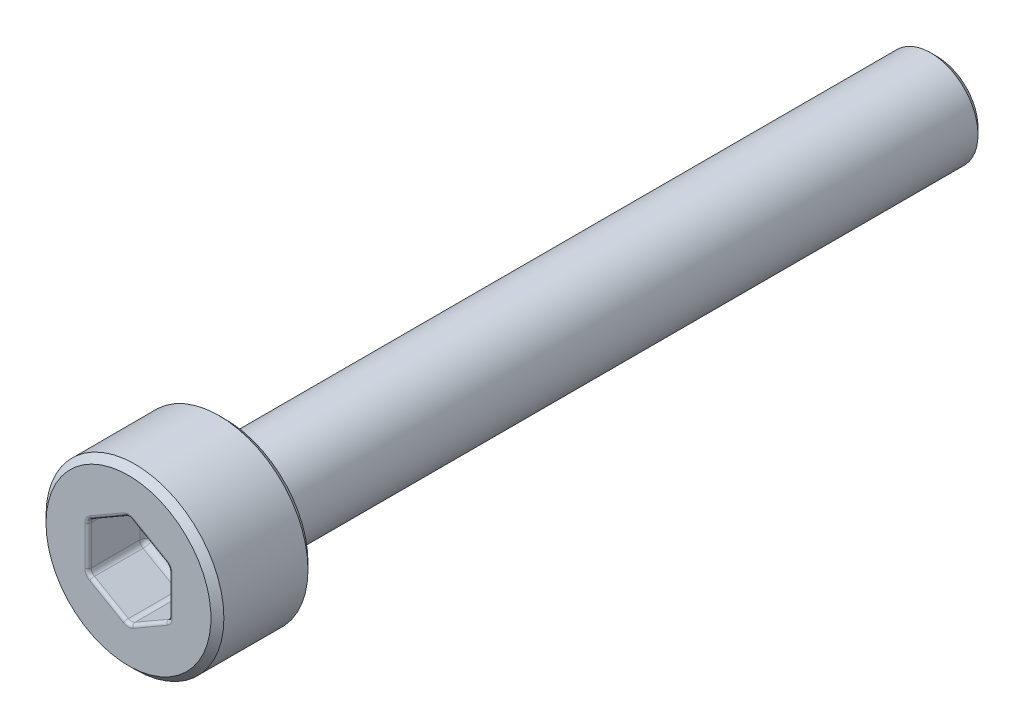
SolidWorks part; units mm, degrees
material "1.4000 (X6Cr13)"
ref_plane "Ebene vorne" through (0, 0, 0) normal (0, 0, 1) x (1, 0, 0)
ref_plane "Ebene oben" through (0, 0, 0) normal (0, 1, 0) x (1, 0, 0)
ref_plane "Ebene rechts" through (0, 0, 0) normal (1, 0, 0) x (0, 0, -1)
sketch "Skizze1" plane through (0, 0, 0) normal (1, 0, 0) x (0, 0, -1)
  line L0 (-21.9199, 0) -> (33.7608, 0) construction
  line L1 (0, 13.9907) -> (0, -9.4798) construction
  line L2 (-3, 0) -> (-3, 2.75)
  line L3 (-3, 2.75) -> (0, 2.75)
  line L4 (0, 2.75) -> (0, 1.465)
  line L5 (0, 1.465) -> (22, 1.465)
  line L6 (22, 1.465) -> (22, 0)
  line L7 (22, 0) -> (-3, 0)
  dimension "D1" = 2.93
  dimension "D2" = 3
  dimension "D3" = 5.5
  dimension "D4" = 22
revolve "Rotation1" add sketch "Skizze1" angle 360 about L0
sketch "Skizze2" plane through (0, 0, 3) normal (0, 0, 1) x (1, 0, 0)
  line L0 (0, 8.6995) -> (0, -7.3778) construction
  line L1 (1.25, -0.7217) -> (1.25, 0.7217)
  line L2 (1.25, 0.7217) -> (0, 1.4434)
  line L3 (0, 1.4434) -> (-1.25, 0.7217)
  line L4 (-1.25, 0.7217) -> (-1.25, -0.7217)
  line L5 (-1.25, -0.7217) -> (0, -1.4434)
  line L6 (0, -1.4434) -> (1.25, -0.7217)
  circle A0 centre (0, 0) radius 1.25 construction
  dimension "D1" = 2.5
extrude "Schnitt-Linear austragen1" cut sketch "Skizze2" against normal blind 1.8
chamfer "Fase1" distance 0.2 angle 45 3 edges at (2.75, 0, 3) (2.75, 0, 0) (1.465, 0, -22)
fillet "Verrundung1" radius 0.2 13 edges at (-0.625, -1.0825, 1.2) (-1.25, 0, 1.2) (-0.625, 1.0825, 1.2) (0.625, 1.0825, 1.2) (1.25, 0, 1.2) (0.625, -1.0825, 1.2) (-1.25, -0.7217, 2.1) (0, -1.4434, 2.1) (1.25, -0.7217, 2.1) (1.25, 0.7217, 2.1) (0, 1.4434, 2.1) (-1.25, 0.7217, 2.1) (1.465, 0, 0)
fillet "Verrundung2" radius 0.1 12 edges at (1.2232, -0.7062, 3) (0.625, -1.0825, 3) (0, -1.4124, 3) (-0.625, -1.0825, 3) (-1.2232, -0.7062, 3) (-1.25, 0, 3) (-1.2232, 0.7062, 3) (-0.625, 1.0825, 3) (0, 1.4124, 3) (0.625, 1.0825, 3) (1.2232, 0.7062, 3) (1.25, 0, 3)
ref_axis "Achse1" through (0, 0, -19.6323) along (0, 0, 1)
